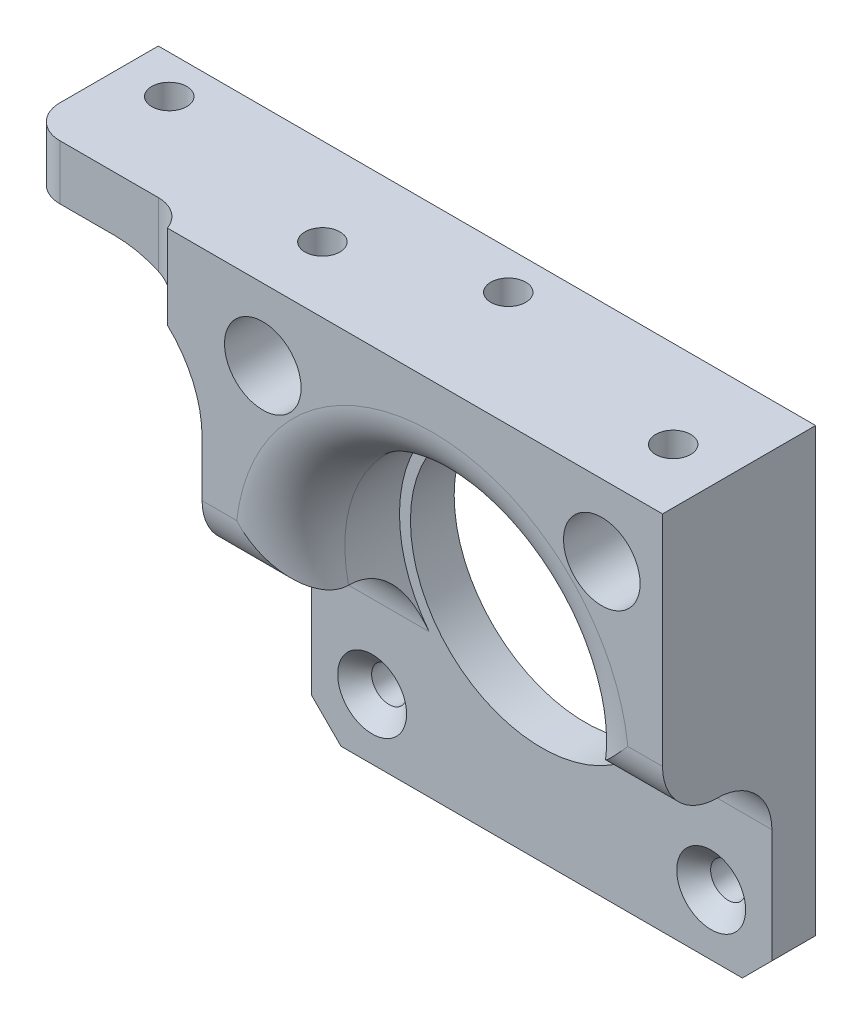
SolidWorks part; units mm, degrees
material "ABS"
ref_plane "Plano frontal" through (0, 0, 0) normal (0, 0, 1) x (1, 0, 0)
ref_plane "Plano superior" through (0, 0, 0) normal (0, 1, 0) x (1, 0, 0)
ref_plane "Plano direito" through (0, 0, 0) normal (1, 0, 0) x (0, 0, -1)
sketch "Esboço1" plane through (0, 0, 0) normal (0, 0, 1) x (1, 0, 0)
  line L1 (108.3727, -351.7657) -> (66.2727, -351.7657)
  line L2 (108.3727, -351.7657) -> (108.3727, -309.6657)
  line L3 (108.3727, -309.6657) -> (66.2727, -309.6657)
  line L4 (66.2727, -351.7657) -> (66.2727, -309.6657)
extrude "Ressalto-extrusão1" add sketch "Esboço1" along normal blind 4
sketch "Esboço2" plane through (0, 0, 4) normal (0, 0, 1) x (1, 0, 0)
  circle A1 centre (87.3227, -330.7157) radius 12
  dimension "D1" = 24
extrude "Corte-extrusão1" cut sketch "Esboço2" against normal blind 8
hole_wizard "Escareado para parafuso de máquina com cabeça chata de M31" positions "Esboço4" profile "Esboço3" countersink size "M3" standard "Ansi Metric" end condition through all
sketch "Esboço4" plane through (0, 0, 4) normal (0, 0, 1) x (1, 0, 0)
  point P0 (102.8227, -346.2157)
  point P3 (102.8227, -315.2157)
  point P6 (71.8227, -315.2157)
  point P9 (71.8227, -346.2157)
sketch "Esboço3" plane through (102.8227, -346.2157, 4) normal (1, 0, 0) x (0, -1, 0)
  line L0 (0, 0) -> (0, 4)
  line L1 (0, 4) -> (1.6, 4)
  line L2 (1.6, 4) -> (1.6, 1.55)
  line L3 (1.6, 1.55) -> (3.15, 0)
  line L5 (3.15, 0) -> (0, 0)
  line L6 (-1.6, 1.55) -> (-3.15, 0) construction
  line L11 (0, -6.35) -> (0, 107.95) construction
  dimension "Thru Hole Dia." = 3.2
  dimension "Thru Hole Depth" = 4
  dimension "Near C'Sink Dia." = 6.3
  dimension "Near C'Sink Angle" = 90
sketch "Esboço5" plane through (0, 0, 4) normal (0, 0, 1) x (1, 0, 0)
  line L0 (108.3727, -351.7657) -> (108.3727, -309.6657) construction
  line L5 (99.9836, -333.6657) -> (108.3727, -333.6657)
  line L6 (66.2727, -309.6657) -> (108.3727, -309.6657)
  line L7 (66.2727, -309.6657) -> (66.2727, -333.6657)
  line L8 (66.2727, -333.6657) -> (74.6618, -333.6657)
  line L9 (108.3727, -309.6657) -> (108.3727, -333.6657)
  arc A0 (99.9836, -333.6657) -> (74.6618, -333.6657) centre (87.3227, -330.7157) ccw
  dimension "D2" = 24
  dimension "D1" = 13
extrude "Ressalto-extrusão2" add sketch "Esboço5" along normal blind 10
sketch "Esboço6" plane through (0, 0, 14) normal (0, 0, 1) x (1, 0, 0)
  circle A0 centre (71.8227, -315.2157) radius 3.5
  circle A1 centre (102.8227, -315.2157) radius 3.5
extrude "Corte-extrusão2" cut sketch "Esboço6" against normal blind 10
hole_wizard "Furo com folga de M31" positions "Esboço8" profile "Esboço7" hole size "M3" standard "ISO" end condition through all
sketch "Esboço8" plane through (0, -309.6657, 0) normal (0, 1, 0) x (1, 0, 0)
  line L0 (87.3227, -14) -> (87.3227, 0) construction
  line L1 (108.3727, -14) -> (66.2727, -14) construction
  line L2 (108.3727, 0) -> (66.2727, 0) construction
  point P0 (103.3591, -8.0127)
  point P13 (71.2863, -8.0127)
sketch "Esboço7" plane through (103.3591, -309.6657, 8.0127) normal (1, 0, 0) x (0, 0, 1)
  line L0 (0, 0) -> (0, 42.1)
  line L1 (0, 42.1) -> (1.6, 42.1)
  line L2 (1.6, 42.1) -> (1.6, 0)
  line L5 (1.6, 0) -> (0, 0)
  line L11 (0, -6.35) -> (0, 107.95) construction
  dimension "Thru Hole Dia." = 3.2
  dimension "Thru Hole Depth" = 42.1
ref_plane "Plano1" through (0, -315.7657, 0) normal (0, -1, 0) x (-1, 0, 0)
sketch "Esboço9" plane through (0, -309.6657, 0) normal (0, -1, 0) x (1, 0, 0)
  line L0 (100.3227, 14) -> (74.3227, 14) construction
  line L1 (95.6994, 14) -> (78.946, 14)
  line L2 (95.6994, 14) -> (95.6994, 1.7904)
  line L3 (95.6994, 1.7904) -> (78.946, 1.7904)
  line L4 (78.946, 14) -> (78.946, 1.7904)
  line L6 (87.3227, 0) -> (87.3227, 14) construction
  line L8 (108.3727, 0) -> (66.2727, 0) construction
extrude "Corte-extrusão3" [suppressed] cut sketch "Esboço9" along normal blind 6
sketch "Esboço10" [suppressed] plane through (0, -315.6657, 0) normal (0, 1, 0) x (1, 0, 0)
  line L0 (83.9727, -5.5101) -> (83.9727, -8.3784) construction
  line L1 (84.9727, -5.5101) -> (84.9727, -8.3784)
  line L2 (82.9727, -5.5101) -> (82.9727, -8.3784)
  line L3 (90.6727, -5.5101) -> (90.6727, -8.3784) construction
  line L4 (91.6727, -5.5101) -> (91.6727, -8.3784)
  line L5 (89.6727, -5.5101) -> (89.6727, -8.3784)
  arc A0 (84.9727, -5.5101) -> (82.9727, -5.5101) centre (83.9727, -5.5101) ccw
  arc A1 (82.9727, -8.3784) -> (84.9727, -8.3784) centre (83.9727, -8.3784) ccw
  arc A2 (91.6727, -5.5101) -> (89.6727, -5.5101) centre (90.6727, -5.5101) ccw
  arc A3 (89.6727, -8.3784) -> (91.6727, -8.3784) centre (90.6727, -8.3784) ccw
  point P2 (83.9727, -6.9442)
  point P9 (90.6727, -6.9442)
  dimension "D1" = 1
  dimension "D2" = 1
extrude "Corte-extrusão4" [suppressed] cut sketch "Esboço10" against normal blind 45
sketch "Esboço12" [suppressed] plane through (0, -333.6657, 0) normal (0, -1, 0) x (1, 0, 0)
  line L0 (82.9727, 6.9442) -> (91.6727, 6.9442) construction
  line L1 (82.9727, 9.8885) -> (91.6727, 9.8885)
  line L2 (82.9727, 4) -> (91.6727, 4)
  line L3 (100.3227, 4) -> (74.3227, 4) construction
  line L4 (100.3227, 4) -> (74.3227, 4) construction
  line L7 (82.9727, 5.5101) -> (82.9727, 8.3784) construction
  line L8 (91.6727, 8.3784) -> (91.6727, 5.5101) construction
  arc A0 (82.9727, 9.8885) -> (82.9727, 4) centre (82.9727, 6.9442) ccw
  arc A1 (91.6727, 4) -> (91.6727, 9.8885) centre (91.6727, 6.9442) ccw
  point P4 (87.3227, 6.9442)
extrude "Corte-extrusão5" [suppressed] cut sketch "Esboço12" against normal blind 16.5
fillet "Filete1" radius 5 5 edges at (87.3227, -317.7157, 14) (104.1781, -333.6657, 14) (70.4673, -333.6657, 14)
fillet "Filete2" [suppressed] radius 0.5
sketch "Esboço13" plane through (0, -351.7657, 0) normal (0, -1, 0) x (1, 0, 0)
  line L1 (74.0363, 9.6004) -> (71.2863, 11.1881)
  line L2 (71.2863, 11.1881) -> (68.5363, 9.6004)
  line L3 (68.5363, 9.6004) -> (68.5363, 6.4249)
  line L4 (68.5363, 6.4249) -> (71.2863, 4.8372)
  line L5 (71.2863, 4.8372) -> (74.0363, 6.4249)
  line L6 (74.0363, 6.4249) -> (74.0363, 9.6004)
  line L7 (106.1091, 9.6004) -> (103.3591, 11.1881)
  line L8 (103.3591, 11.1881) -> (100.6091, 9.6004)
  line L9 (100.6091, 9.6004) -> (100.6091, 6.4249)
  line L10 (100.6091, 6.4249) -> (103.3591, 4.8372)
  line L11 (103.3591, 4.8372) -> (106.1091, 6.4249)
  line L12 (106.1091, 6.4249) -> (106.1091, 9.6004)
  circle A2 centre (71.2863, 8.0127) radius 2.75 construction
  circle A3 centre (103.3591, 8.0127) radius 2.75 construction
extrude "Corte-extrusão6" cut sketch "Esboço13" against normal blind 22.5
chamfer "Chanfro1" distance 2.7 angle 45 2 edges at (66.2727, -351.7657, 2) (108.3727, -351.7657, 2)
chamfer "Chanfro2" [suppressed] distance 0.1 angle 45
sketch "Esboço14" plane through (0, -309.6657, 0) normal (0, 1, 0) x (1, 0, 0)
  line L1 (66.2727, -14) -> (73.7769, -14)
  line L2 (66.2727, -14) -> (66.2727, -11.5964)
  line L3 (66.2727, -11.5964) -> (73.7769, -11.5964)
  line L4 (73.7769, -14) -> (73.7769, -11.5964)
  spline S0 degree 3 poles (69.4398, -14) (69.5727, -14) (69.7086, -13.9932) (69.9783, -13.9667) (70.1135, -13.9469) (70.5199, -13.8685) (70.7932, -13.7906) (71.6105, -13.4813) (72.1417, -13.183) (72.9065, -12.5724) (73.1545, -12.3413) (73.5003, -11.9557) (73.6116, -11.8203) (73.8248, -11.5335) (73.9271, -11.3813) (74.1172, -11.0616) (74.2044, -10.8953) (74.3603, -10.5478) (74.4293, -10.3656) (74.5999, -9.7988) (74.6618, -9.4073) (74.6618, -9) knots 0 0 0 0 0.0625 0.0625 0.125 0.125 0.25 0.25 0.5 0.5 0.625 0.625 0.6875 0.6875 0.75 0.75 0.8125 0.8125 0.875 0.875 1 1 1 1 construction
extrude "Corte-extrusão7" [suppressed] cut sketch "Esboço14" against normal through all
sketch "Sketch2" plane through (0, -309.6657, 0) normal (0, 1, 0) x (1, 0, 0)
  line L9 (66.2727, -14) -> (108.3727, -14)
  line L10 (108.3727, -14) -> (108.3727, 0)
  line L11 (108.3727, 0) -> (66.2727, 0)
  line L12 (66.2727, 0) -> (66.2727, -14)
  line L17 (66.2727, -14) -> (108.3727, -14)
  line L18 (108.3727, -14) -> (108.3727, 0)
  line L19 (108.3727, 0) -> (66.2727, 0)
  line L20 (66.2727, 0) -> (66.2727, -14)
  circle A0 centre (71.2863, -8.0127) radius 1.6 construction
  circle A1 centre (103.3591, -8.0127) radius 1.6 construction
  circle A2 centre (71.2863, -8.0127) radius 1.6
  circle A3 centre (103.3591, -8.0127) radius 1.6
  dimension "D1" = 0
extrude "Boss-Extrude1" add sketch "Sketch2" along normal blind 1
chamfer "Chanfro3" [suppressed] distance 0.1 angle 45
sketch "Sketch3" plane through (0, 0, 14) normal (0, 0, 1) x (1, 0, 0)
  line L1 (66.2727, -308.6657) -> (79.2727, -308.6657)
  line L2 (66.2727, -308.6657) -> (66.2727, -311.7157)
  line L3 (66.2727, -311.7157) -> (79.2727, -311.7157)
  line L7 (79.2727, -311.7157) -> (79.2727, -308.6657)
  dimension "13" = 13
extrude "Boss-Extrude2" [suppressed] add sketch "Sketch3" along normal blind 5.5 and the other way blind 3.6
fillet "Fillet1" [suppressed] radius 6
fillet "Fillet2" [suppressed] radius 3
sketch "Sketch4" [suppressed] plane through (0, -351.7657, 0) normal (0, -1, 0) x (1, 0, 0)
  line L1 (79.2727, 19.5) -> (74.8946, 19.5)
  line L2 (79.2727, 19.5) -> (79.2727, 17.6667)
  line L3 (79.2727, 17.6667) -> (74.8946, 17.6667)
  line L4 (74.8946, 19.5) -> (74.8946, 17.6667)
extrude "Cut-Extrude1" [suppressed] cut sketch "Sketch4" against normal blind 49
sketch "Esboço15" plane through (0, -308.6657, 0) normal (0, -1, 0) x (1, 0, 0)
  line L14 (83.769, 157) -> (63.269, 157)
  line L15 (63.269, 157) -> (63.269, 15)
  line L16 (60.269, 12) -> (51.269, 12)
  line L17 (48.269, 9) -> (48.269, -2)
  line L18 (47.269, -3) -> (-112.731, -3)
  line L19 (-113.731, -2) -> (-113.731, 9)
  line L20 (-116.731, 12) -> (-129.731, 12)
  line L21 (-132.731, 15) -> (-132.731, 133)
  line L22 (-132.7305, 133.0571) -> (-132.731, 133.0571)
  line L23 (-132.731, 133.0571) -> (-132.731, 157)
  line L24 (-132.731, 157) -> (-154.731, 157)
  line L25 (-157.731, 154) -> (-157.731, -32)
  line L26 (-156.731, -33) -> (86.769, -33)
  line L27 (86.769, -33) -> (86.769, 154)
  line L28 (83.769, 157) -> (63.269, 157)
  line L29 (63.269, 157) -> (63.269, 15)
  line L30 (60.269, 12) -> (51.269, 12)
  line L31 (48.269, 9) -> (48.269, -2)
  line L32 (47.269, -3) -> (-112.731, -3)
  line L33 (-113.731, -2) -> (-113.731, 9)
  line L34 (-116.731, 12) -> (-129.731, 12)
  line L35 (-132.731, 15) -> (-132.731, 133)
  line L36 (-132.7305, 133.0571) -> (-132.731, 133.0571)
  line L37 (-132.731, 133.0571) -> (-132.731, 157)
  line L38 (-132.731, 157) -> (-154.731, 157)
  line L39 (-157.731, 154) -> (-157.731, -32)
  line L40 (-156.731, -33) -> (86.769, -33)
  line L41 (86.769, -33) -> (86.769, 154)
  arc A10 (60.269, 12) -> (63.269, 15) centre (60.269, 15) ccw
  arc A11 (51.269, 12) -> (48.269, 9) centre (51.269, 9) ccw
  arc A12 (47.269, -3) -> (48.269, -2) centre (47.269, -2) ccw
  arc A13 (-113.731, -2) -> (-112.731, -3) centre (-112.731, -2) ccw
  arc A14 (-113.731, 9) -> (-116.731, 12) centre (-116.731, 9) ccw
  arc A15 (-132.731, 15) -> (-129.731, 12) centre (-129.731, 15) ccw
  arc A16 (-132.7305, 133.0571) -> (-132.731, 133) centre (-129.731, 133) ccw
  arc A17 (-154.731, 157) -> (-157.731, 154) centre (-154.731, 154) ccw
  arc A18 (-157.731, -32) -> (-156.731, -33) centre (-156.731, -32) ccw
  arc A19 (86.769, 154) -> (83.769, 157) centre (83.769, 154) ccw
  arc A20 (60.269, 12) -> (63.269, 15) centre (60.269, 15) ccw
  arc A21 (51.269, 12) -> (48.269, 9) centre (51.269, 9) ccw
  arc A22 (47.269, -3) -> (48.269, -2) centre (47.269, -2) ccw
  arc A23 (-113.731, -2) -> (-112.731, -3) centre (-112.731, -2) ccw
  arc A24 (-113.731, 9) -> (-116.731, 12) centre (-116.731, 9) ccw
  arc A25 (-132.731, 15) -> (-129.731, 12) centre (-129.731, 15) ccw
  arc A26 (-132.7305, 133.0571) -> (-132.731, 133) centre (-129.731, 133) ccw
  arc A27 (-154.731, 157) -> (-157.731, 154) centre (-154.731, 154) ccw
  arc A28 (-157.731, -32) -> (-156.731, -33) centre (-156.731, -32) ccw
  arc A29 (86.769, 154) -> (83.769, 157) centre (83.769, 154) ccw
  point P4 (63.269, 15)
  dimension "D1" = 0
sketch "Esboço16" plane through (0, -308.6657, 0) normal (0, -1, 0) x (1, 0, 0)
  line L0 (48.269, -2) -> (48.269, 9) construction
  line L1 (66.2727, 0) -> (48.269, 0)
  line L2 (66.2727, 0) -> (66.2727, 14)
  line L3 (66.2727, 14) -> (63.0974, 14)
  line L5 (51.269, 12) -> (60.269, 12) construction
  line L6 (48.269, 0) -> (48.269, 9)
  line L7 (51.269, 12) -> (60.269, 12)
  arc A0 (60.269, 12) -> (63.269, 15) centre (60.269, 15) ccw construction
  arc A1 (51.269, 12) -> (48.269, 9) centre (51.269, 9) ccw construction
  arc A2 (60.269, 12) -> (63.0974, 14) centre (60.269, 15) ccw
  arc A3 (51.269, 12) -> (48.269, 9) centre (51.269, 9) ccw
extrude "Ressalto-extrusão3" add sketch "Esboço16" along normal blind 5
fillet "Filete3" radius 10 1 edges at (66.2727, -313.6657, 7)
sketch "Esboço17" plane through (0, -308.6657, 0) normal (0, 1, 0) x (1, 0, 0)
  circle A0 centre (83.769, -3.5) radius 1.6
  circle A1 centre (52.769, -3.5) radius 1.6
extrude "Corte-extrusão8" cut sketch "Esboço17" against normal blind 31
sketch "Esboço18" plane through (0, -313.6657, 0) normal (0, -1, 0) x (1, 0, 0)
  line L1 (52.769, 6.675) -> (50.0194, 5.0875)
  line L2 (50.0194, 5.0875) -> (50.0194, 1.9125)
  line L3 (50.0194, 1.9125) -> (52.769, 0.325)
  line L4 (52.769, 0.325) -> (55.5186, 1.9125)
  line L5 (55.5186, 1.9125) -> (55.5186, 5.0875)
  line L6 (55.5186, 5.0875) -> (52.769, 6.675)
  line L7 (83.769, 6.675) -> (81.0194, 5.0875)
  line L8 (81.0194, 5.0875) -> (81.0194, 1.9125)
  line L9 (81.0194, 1.9125) -> (83.769, 0.325)
  line L10 (83.769, 0.325) -> (86.5186, 1.9125)
  line L11 (86.5186, 1.9125) -> (86.5186, 5.0875)
  line L12 (86.5186, 5.0875) -> (83.769, 6.675)
  circle A0 centre (52.769, 3.5) radius 2.7496 construction
  circle A1 centre (83.769, 3.5) radius 2.7496 construction
  dimension "D1" = 6.35
  dimension "D2" = 6.35
extrude "Corte-extrusão9" cut sketch "Esboço18" along normal blind 8 and the other way blind 2
